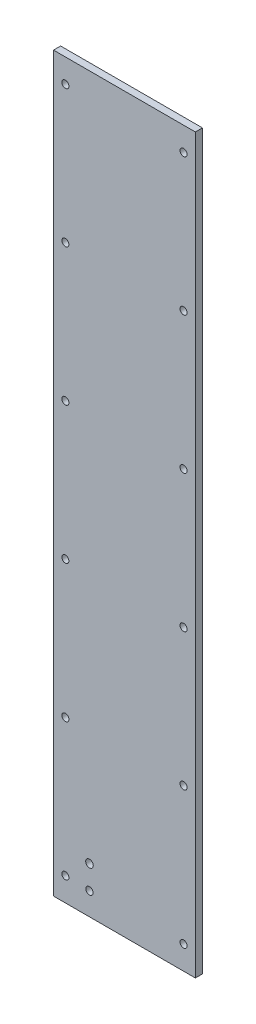
SolidWorks part; units mm, degrees
ref_plane "Plan de face" through (0, 0, 0) normal (0, 0, 1) x (1, 0, 0)
ref_plane "Plan de dessus" through (0, 0, 0) normal (0, 1, 0) x (1, 0, 0)
ref_plane "Plan de droite" through (0, 0, 0) normal (1, 0, 0) x (0, 0, -1)
sketch "Esquisse1" plane through (0, 0, 0) normal (0, 0, 1) x (1, 0, 0)
  line L0 (-30, 0) -> (30, 0) construction
  line L1 (30, -155) -> (-30, -155)
  line L2 (30, -155) -> (30, 155)
  line L3 (30, 155) -> (-30, 155)
  line L4 (-30, -155) -> (-30, 155)
  line L5 (30, -155) -> (-30, 155) construction
  line L6 (30, 155) -> (-30, -155) construction
  line L7 (-30, -155) -> (-20, -155)
  line L8 (-30, -155) -> (-30, -150)
  line L13 (-30, 155) -> (-20, 155)
  line L14 (-30, 155) -> (-30, 150)
  line L15 (-25, -155) -> (-25, 155) construction
  line L16 (0, 155) -> (0, -155) construction
  line L17 (-25, -145) -> (-25, -87) construction
  circle A0 centre (-25, -145) radius 1.5
  circle A1 centre (-25, -87) radius 1.5
  circle A2 centre (-25, -29) radius 1.5
  circle A3 centre (-25, 29) radius 1.5
  circle A4 centre (-25, 87) radius 1.5
  circle A5 centre (-25, 145) radius 1.5
  circle A6 centre (25, -87) radius 1.5
  circle A7 centre (25, -145) radius 1.5
  circle A8 centre (25, -29) radius 1.5
  circle A9 centre (25, 29) radius 1.5
  circle A10 centre (25, 87) radius 1.5
  circle A11 centre (25, 145) radius 1.5
  circle A12 centre (-14.8, -135.4553) radius 1.6
  circle A14 centre (-14.8, -145.4553) radius 1.55
  circle A16 centre (-14.8, -135.4553) radius 1.5 construction
  circle A17 centre (-14.8, -145.4553) radius 1.5 construction
  point P0 (0, 0)
  dimension "D5" = 3
  dimension "D1" = 60
  dimension "D2" = 310
  dimension "D7" = 58
  dimension "D8" = 6
extrude "Boss.-Extru.1" add sketch "Esquisse1" along normal blind 3 contours L3 L4 L1 L2 A10 A8 A6 A5 A4 A3 A2 A1 A0 A7 A9 A11 region at (0.0125, 0.1182, 0)
